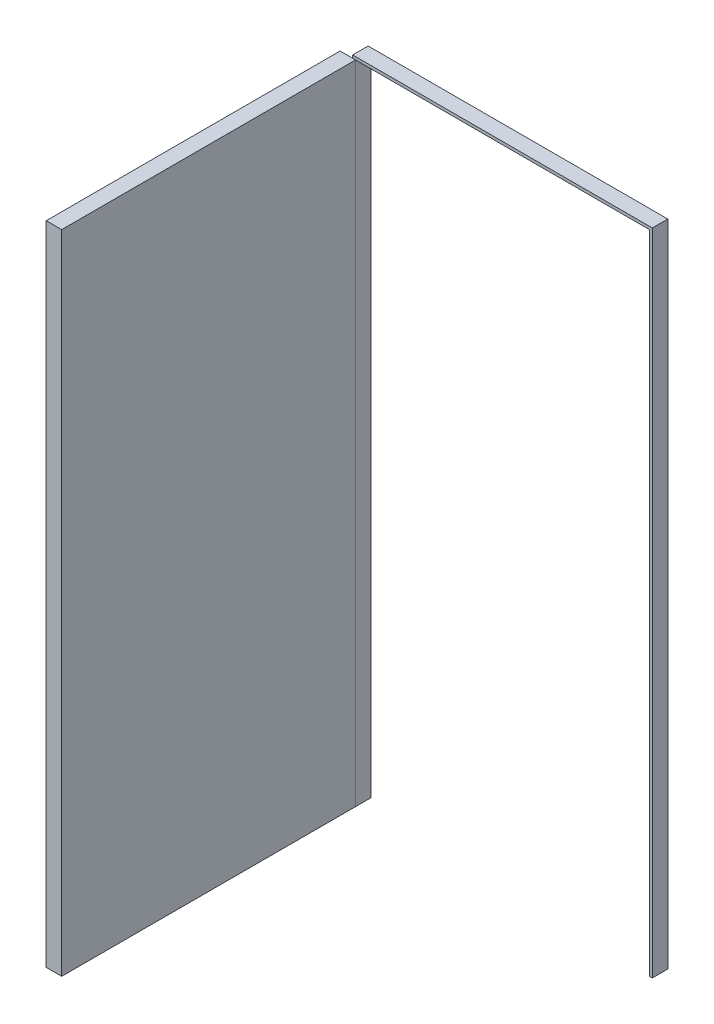
SolidWorks part; units mm, degrees
ref_plane "Front" through (0, 0, 0) normal (0, 0, 1) x (1, 0, 0)
ref_plane "Top" through (0, 0, 0) normal (0, 1, 0) x (1, 0, 0)
ref_plane "Right" through (0, 0, 0) normal (1, 0, 0) x (0, 0, -1)
sketch "Sketch1" plane through (0, 0, 0) normal (0, 0, 1) x (1, 0, 0)
  line L0 (965.2, 2114.55) -> (965.2, -2133.6)
  line L1 (-984.25, 2133.6) -> (984.25, 2133.6)
  line L2 (-984.25, 2133.6) -> (-984.25, -2133.6)
  line L3 (-984.25, -2133.6) -> (984.25, -2133.6) construction
  line L4 (984.25, 2133.6) -> (984.25, -2133.6)
  line L5 (-984.25, 2133.6) -> (984.25, -2133.6) construction
  line L6 (-984.25, -2133.6) -> (984.25, 2133.6) construction
  line L7 (-965.2, 2114.55) -> (965.2, 2114.55)
  line L8 (-965.2, 2114.55) -> (-965.2, -2133.6)
  line L9 (-984.25, -2133.6) -> (-965.2, -2133.6)
  line L10 (965.2, -2133.6) -> (984.25, -2133.6)
  point P0 (0, 0)
  dimension "D1" = 4267.2
  dimension "D3" = 1930.4
  dimension "D2" = 19.05
extrude "Boss-Extrude1" add sketch "Sketch1" along normal blind 101.6
sketch "Sketch2" plane through (0, -2133.6, 0) normal (0, -1, 0) x (1, 0, 0)
  line L0 (-965.2, 101.6) -> (-965.2, 2032)
  line L1 (-965.2, 2032) -> (-1066.8, 2032)
  line L2 (-1066.8, 2032) -> (-1066.8, 101.6)
  line L3 (-1066.8, 101.6) -> (-965.2, 101.6)
  line L4 (-965.2, 0) -> (965.2, 0) construction
  dimension "D1" = 101.6
  dimension "D2" = 90
extrude "Boss-Extrude2" add sketch "Sketch2" against normal up to surface (4248.15 mm away) separate body up to face at (0, 2114.55, 50.8)
